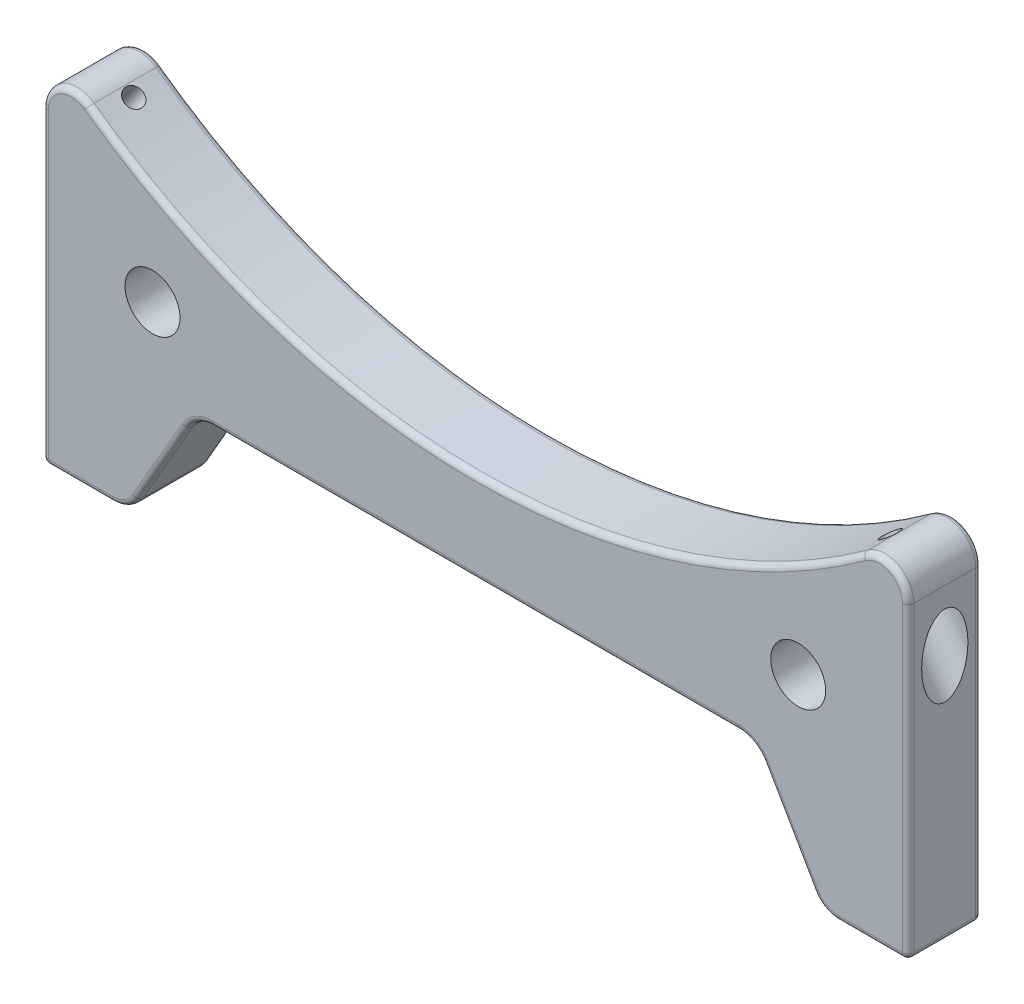
SolidWorks part; units mm, degrees
material "6061-T6 (SS)"
ref_plane "Front Plane" through (0, 0, 0) normal (0, 0, 1) x (1, 0, 0)
ref_plane "Top Plane" through (0, 0, 0) normal (0, 1, 0) x (1, 0, 0)
ref_plane "Right Plane" through (0, 0, 0) normal (1, 0, 0) x (0, 0, -1)
sketch "Sketch1" plane through (0, 0, 0) normal (0, 0, 1) x (1, 0, 0)
  line L0 (0, 0) -> (0, -150) construction
  line L1 (-75, -150) -> (75, -150)
  line L2 (75, -150) -> (75, -86.2525)
  line L3 (-75, -150) -> (-75, -86.2525)
  circle A0 centre (0, 0) radius 114.3
  dimension "D1" = 228.6
  dimension "D2" = 150
  dimension "D3" = 75
extrude "Boss-Extrude1" add sketch "Sketch1" along normal blind 12.7 contours L0 A0 L3 L1 | A0 L0 L1 L2 region at (41.3176, -126.9812, 0) region at (-41.3176, -126.9812, 0)
ref_plane "Plane1" through (0, 0, 6.35) normal (0, 0, 1) x (1, 0, 0)
sketch "Sketch2" plane through (0, 0, 6.35) normal (0, 0, 1) x (1, 0, 0)
  line L0 (0, -114.3) -> (0, -150) construction
  line L1 (-75, -150) -> (75, -150) construction
  line L2 (0, -114.3) -> (0, 0) construction
  line L3 (-75, -150) -> (-75, -86.2525) construction
  line L4 (75, -150) -> (75, -86.2525) construction
  line L5 (-75, -150) -> (-75, -86.2525)
  line L6 (75, -150) -> (75, -86.2525)
  line L7 (-75, -150) -> (75, -150)
  line L8 (0, 0) -> (-75, -107.1111) construction
  arc A0 (-75, -86.2525) -> (75, -86.2525) centre (0, 0) ccw construction
  arc A1 (-75, -86.2525) -> (75, -86.2525) centre (0, 0) ccw
  point P3 (-65.5598, -93.6291)
  dimension "D1" = 35
ref_plane "Plane4" through (-65.5598, -93.6291, 6.35) normal (0.5736, 0.8192, 0) x (-0.8192, 0.5736, 0)
ref_plane "Plane5" through (-75.8842, -108.3738, 0) normal (0.5736, 0.8192, 0) x (-0.8192, 0.5736, 0)
sketch "Sketch14" plane through (-75.8842, -108.3738, 0) normal (0.5736, 0.8192, 0) x (-0.8192, 0.5736, 0)
  circle A0 centre (0, 6.35) radius 1.632
  circle A1 centre (0, 6.35) radius 4
  dimension "D1" = 3.2639
  dimension "D2" = 8
extrude "Cut-Extrude1" cut sketch "Sketch14" along normal blind 12.7 and the other way blind 12.7 contours A0 | A1 A0 region at (-75.8842, -108.3738, 6.35) region at (-72.7002, -110.6032, 6.35)
extrude "Cut-Extrude2" cut sketch "Sketch14<3>" along normal through all contours A0 region at (-75.8842, -108.3738, 6.35)
sketch "Sketch14<3>" plane through (-75.8842, -108.3738, 0) normal (0.5736, 0.8192, 0) x (-0.8192, 0.5736, 0) same geometry as "Sketch14"
mirror "Mirror1" about plane through (0, 0, 0) normal (1, 0, 0) of "Cut-Extrude2", "Cut-Extrude1"
sketch "Sketch15" plane through (0, 0, 12.7) normal (0, 0, 1) x (1, 0, 0)
  line L0 (0, -114.3) -> (0, -150) construction
  line L1 (-60, -150) -> (-48.453, -130)
  line L2 (-48.453, -130) -> (48.453, -130)
  line L3 (-75, -150) -> (75, -150)
  line L4 (75, -150) -> (75, -86.2525)
  line L5 (-75, -86.2525) -> (-75, -150)
  line L6 (-75, -150) -> (75, -150)
  line L7 (75, -150) -> (75, -86.2525)
  line L8 (-75, -86.2525) -> (-75, -150)
  line L9 (60, -150) -> (48.453, -130)
  arc A1 (-75, -86.2525) -> (75, -86.2525) centre (0, 0) ccw
  arc A2 (-75, -86.2525) -> (75, -86.2525) centre (0, 0) ccw
  point P11 (0, -130)
  line M5 (-75, -150) -> (75, -150)
  dimension "D2" = 20
  dimension "D3" = 60
  dimension "D4" = 60
  dimension "D1" = 0
extrude "Cut-Extrude3" cut sketch "Sketch15" against normal through all contours L0 L2 L1 M5 | L2 L0 L6 L9 region at (27.2157, -140.3549, 12.7) region at (-27.2157, -140.3549, 12.7)
fillet "Fillet1" radius 5 6 edges at (75, -86.2525, 6.35) (60, -150, 6.35) (48.453, -130, 6.35) (-48.453, -130, 6.35) (-60, -150, 6.35) (-75, -86.2525, 6.35)
fillet "Fillet2" radius 1 30 edges at (60.3868, -149.3301, 0) (54.2265, -140, 0) (60.3868, -149.3301, 12.7) (68.9434, -150, 0) (48.0662, -130.6699, 0) (54.2265, -140, 12.7) (75, -150, 6.35) (68.9434, -150, 12.7) (75, -123.3024, 0) (0, -130, 0) (48.0662, -130.6699, 12.7) (75, -123.3024, 12.7) (72.2728, -92.1512, 0) (-48.0662, -130.6699, 0) (0, -130, 12.7) (72.2728, -92.1512, 12.7) (0, -114.3, 0) (-54.2265, -140, 0) (-48.0662, -130.6699, 12.7) (0, -114.3, 12.7) (-72.2728, -92.1512, 0) (-60.3868, -149.3301, 0) (-54.2265, -140, 12.7) (-72.2728, -92.1512, 12.7) (-75, -123.3024, 0) (-68.9434, -150, 0) (-60.3868, -149.3301, 12.7) (-75, -123.3024, 12.7) (-75, -150, 6.35) (-68.9434, -150, 12.7)
ref_axis "Axis1" through (6.0389, 8.6244, 6.35) along (-0.5736, -0.8192, 0)
ref_axis "Axis2" through (-4.8739, 6.9607, 6.35) along (0.5736, -0.8192, 0)
sketch "Sketch16" plane through (0, 0, 12.7) normal (0, 0, 1) x (1, 0, 0)
  line L0 (-62.8868, -150) -> (-74, -150) construction
  line L1 (-75, -149) -> (-75, -96.6048) construction
  line L2 (0, -129) -> (0, -115.3) construction
  line L3 (-45.5662, -129) -> (45.5662, -129) construction
  circle A0 centre (-55.95, -116.345) radius 4.7625
  arc A1 (-67.653, -93.3658) -> (67.653, -93.3658) centre (0, 0) ccw construction
  circle A2 centre (55.95, -116.345) radius 4.7625
  dimension "D1" = 9.525
  dimension "D2" = 33.655
  dimension "D3" = 19.05
extrude "Cut-Extrude4" cut sketch "Sketch16" against normal through all
